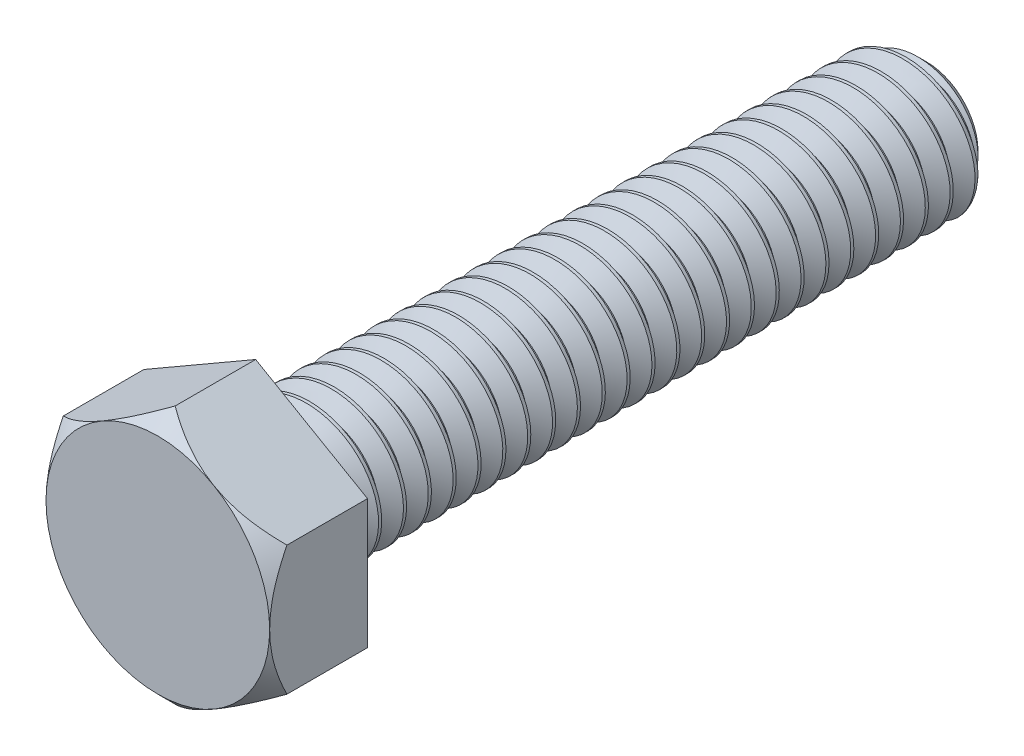
SolidWorks part; units mm, degrees
material "Plain Carbon Steel"
ref_plane "Front Plane" through (0, 0, 0) normal (0, 0, 1) x (1, 0, 0)
ref_plane "Top Plane" through (0, 0, 0) normal (0, 1, 0) x (1, 0, 0)
ref_plane "Right Plane" through (0, 0, 0) normal (1, 0, 0) x (0, 0, -1)
sketch "Sketch1" plane through (0, 0, 0) normal (1, 0, 0) x (0, 0, -1)
  line L0 (0, 0) -> (43.6562, 0) construction
  line L1 (0, -6.35) -> (0, 6.35) construction
  line L2 (43.6562, -3.9751) -> (43.6562, 3.9751) construction
  line L3 (43.6562, 3.9751) -> (42.2451, 3.9751) construction
  point P3 (43.6562, 0)
  point P6 (0, 0)
  point P7 (5.5562, 0)
  point P8 (41.5396, -3.9751)
  point P12 (43.6562, 0)
  dimension "Hex Width" = 12.7
  dimension "Hex Height" = 5.5562
  dimension "Length" = 38.1
  dimension "Thread Length" = 38.1
  dimension "OD" = 7.9502
  dimension "Pitch" = 1.4111
  dimension "D1" = 2.1167
sketch "Sketch2" plane through (0, 0, 0) normal (0, 0, 1) x (1, 0, 0)
  line L0 (0, -3.9751) -> (0, 3.9751) construction
  line L1 (6.35, 3.6662) -> (0, 7.3323)
  line L2 (0, 7.3323) -> (-6.35, 3.6662)
  line L3 (-6.35, 3.6662) -> (-6.35, -3.6662)
  line L4 (-6.35, -3.6662) -> (0, -7.3323)
  line L5 (0, -7.3323) -> (6.35, -3.6662)
  line L6 (6.35, -3.6662) -> (6.35, 3.6662)
  circle A0 centre (0, 0) radius 6.35 construction
  dimension "D1" = 12.7
extrude "Boss-Extrude1" add sketch "Sketch2" against normal up to vertex (5.5563 mm away) up to point (0, 0, -5.5562)
sketch "Sketch3" plane through (0, 0, -5.5562) normal (0, 0, -1) x (-1, 0, 0)
  circle A0 centre (0, 0) radius 3.9751
  dimension "D1" = 7.9502
extrude "Boss-Extrude2" add sketch "Sketch3" along normal up to vertex (38.1 mm away) up to point (0, 0, -43.6562)
chamfer "Chamfer1" distance 1.0583 angle 45 1 edges at (-3.9751, 0, -43.6562)
sketch "Sketch4" plane through (0, 0, 0) normal (0, 0, 1) x (1, 0, 0)
  circle A0 centre (0, 0) radius 6.35 construction
  circle A1 centre (0, 0) radius 6.35
extrude "Cut-Extrude1" cut sketch "Sketch4" against normal through all draft 45 flip side to cut
sketch "Sketch5" plane through (0, 0, -43.6562) normal (0, 0, -1) x (-1, 0, 0)
  circle A2 centre (0, 0) radius 3.9751 construction
  circle A3 centre (0, 0) radius 3.9751
curve "Helix/Spiral1" pitch 1.4111 height 39.5111 turns 28
sketch "Sketch6" plane through (0, 0, 0) normal (1, 0, 0) x (0, 0, -1)
  line L6 (43.5681, 4.1279) -> (44.2736, 2.9058) construction
  line L7 (44.2736, 2.9058) -> (44.9792, 4.1279) construction
  line L8 (44.9792, 4.1279) -> (43.5681, 4.1279) construction
  line L9 (44.2736, 4.1279) -> (44.2736, 3.9751) construction
  line L10 (44.2736, 2.9058) -> (44.2736, 3.0586) construction
  line L11 (43.6562, 3.9751) -> (44.891, 3.9751) construction
  line L12 (43.6122, 4.0515) -> (44.9351, 4.0515)
  line L13 (44.1854, 3.0586) -> (44.3618, 3.0586)
  line L14 (43.6122, 4.0515) -> (44.1854, 3.0586)
  line L15 (44.3618, 3.0586) -> (44.9351, 4.0515)
  point P19 (44.2736, 3.9751)
  point P22 (44.2736, 4.0515)
  point P27 (44.2736, 3.0586)
  dimension "D4" = 1.4111
  dimension "D5" = 0.1764
sweep "Cut-Sweep1" cut profiles "Sketch6" path "Helix/Spiral1"
equation "\"D1@Sketch2\"=\"Hex Width@Sketch1\""
equation "\"D1@Sketch3\"=\"OD@Sketch1\""
equation "\"D1@Chamfer1\"=\"Pitch@Sketch1\"*.75"
equation "\"D3@Helix/Spiral1\"=\"Thread Length@Sketch1\"+\"Pitch@Sketch1\""
equation "\"D4@Helix/Spiral1\"=\"Pitch@Sketch1\""
equation "\"D1@Sketch1\"=\"Pitch@Sketch1\"*1.5"
equation "\"D4@Sketch6\"=\"Pitch@Sketch1\""
equation "\"D5@Sketch6\"=\"D4@Sketch6\"/8"
